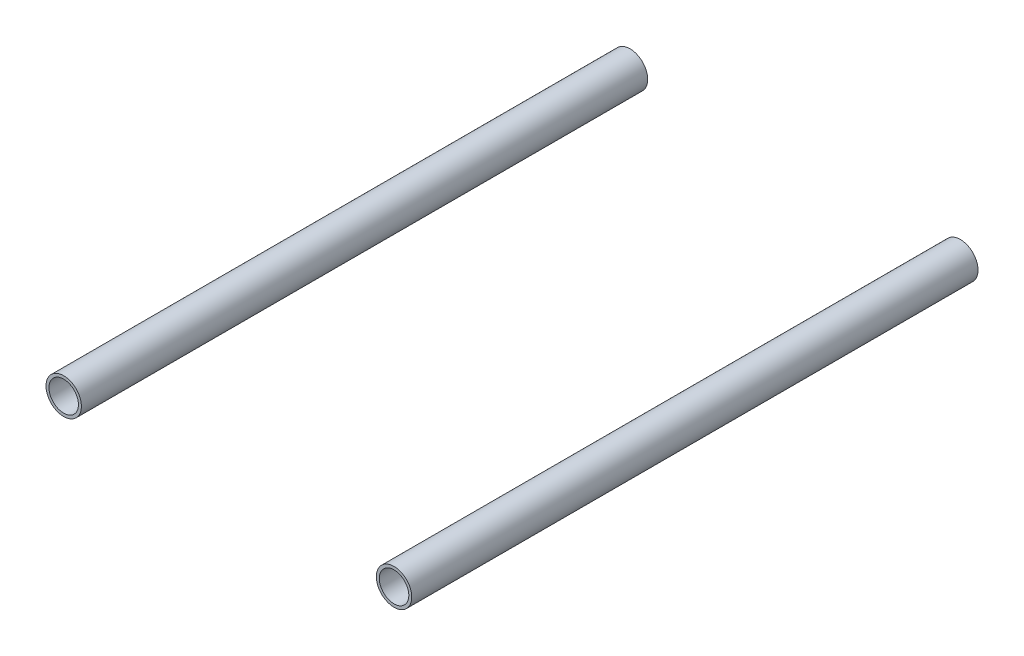
SolidWorks part; units mm, degrees
material "Thornel Mat VMA"
ref_plane "Front Plane" through (0, 0, 0) normal (0, 0, 1) x (1, 0, 0)
ref_plane "Top Plane" through (0, 0, 0) normal (0, 1, 0) x (1, 0, 0)
ref_plane "Right Plane" through (0, 0, 0) normal (1, 0, 0) x (0, 0, -1)
sketch "Sketch1" plane through (0, 0, 0) normal (0, 0, 1) x (1, 0, 0)
  circle A0 centre (0, 0) radius 9.525
  circle A1 centre (177.8, 0) radius 9.525
  circle A2 centre (0, 0) radius 7.9375
  circle A3 centre (177.8, 0) radius 7.9375
  dimension "D1" = 19.05
  dimension "D4" = 1.5875
  dimension "D3" = 177.8
extrude "Boss-Extrude1" add sketch "Sketch1" along normal mid plane 304.8 contours A0 | A1 region at (-9.2556, 0, 0) region at (168.5444, 0, 0)
